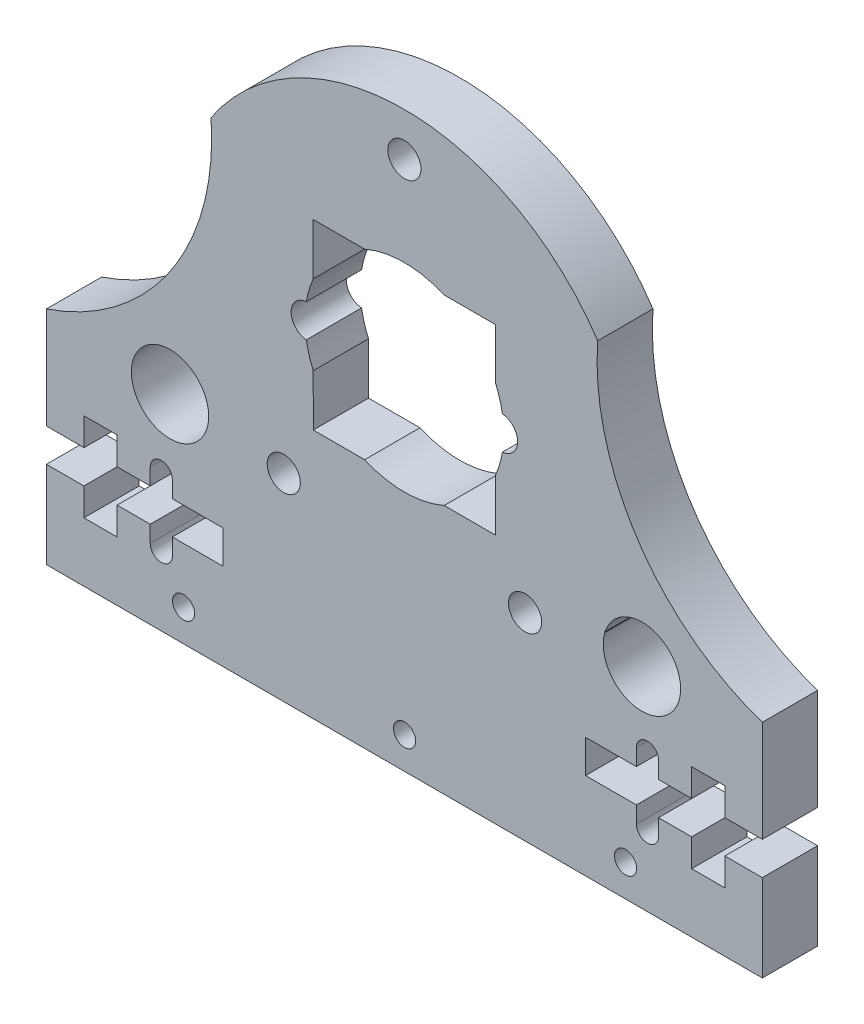
SolidWorks part; units mm, degrees
ref_plane "Front Plane" through (0, 0, 0) normal (0, 0, 1) x (1, 0, 0)
ref_plane "Top Plane" through (0, 0, 0) normal (0, 1, 0) x (1, 0, 0)
ref_plane "Right Plane" through (0, 0, 0) normal (1, 0, 0) x (0, 0, -1)
sketch "Sketch1" plane through (0, 0, 0) normal (0, 0, 1) x (1, 0, 0)
  line L0 (7.049, 19.6325) -> (17.9731, -10.4272)
  line L1 (-10.7531, -20.4888) -> (10.9241, -20.4888)
  line L2 (-7.0493, 19.6315) -> (-17.9689, -10.4301)
  line L68 (-32.396, -10.8383) -> (-32.396, -30.8817)
  line L69 (-32.396, -10.8383) -> (32.396, -10.8383)
  line L70 (32.396, -10.8383) -> (32.396, -30.8817)
  line L71 (-32.396, -30.8817) -> (32.396, -30.8817)
  line L72 (-32.396, -10.8383) -> (32.396, -30.8817) construction
  line L73 (32.396, -10.8383) -> (-32.396, -30.8817) construction
  line L83 (8.2458, 8.2543) -> (3.5926, 8.2519)
  line L84 (-3.6012, 8.2481) -> (-8.2543, 8.2457)
  line L85 (-8.2543, 8.2457) -> (-8.2519, 3.5926)
  line L86 (-8.2481, -3.6012) -> (-8.2457, -8.2543)
  line L87 (-8.2457, -8.2543) -> (-3.5926, -8.2519)
  line L88 (3.6012, -8.2481) -> (8.2543, -8.2457)
  line L89 (8.2543, -8.2457) -> (8.2519, -3.5217)
  line L90 (8.2481, 3.672) -> (8.2458, 8.2543)
  arc A0 (7.049, 19.6325) -> (-7.0493, 19.6315) centre (0, 17.0709) ccw
  arc A1 (10.9241, -20.4888) -> (17.9731, -10.4272) centre (10.9241, -12.9888) ccw
  arc A2 (-17.9689, -10.4301) -> (-10.7531, -20.4888) centre (-10.9196, -12.9907) ccw
  circle A3 centre (0, 17.0709) radius 1.5
  circle A4 centre (10.9241, -12.9888) radius 1.5
  circle A5 centre (-10.9196, -12.9907) radius 1.5
  arc A6 (-28.1118, -10.8383) -> (-16.6025, -6.6683) centre (-21.209, -11.9221) cw
  arc A7 (16.6787, -6.8654) -> (28.4035, -10.8383) centre (21.5008, -11.9221) cw
  circle A8 centre (0, 0.0709) radius 17 construction
  circle A78 centre (21.5008, -11.9221) radius 3.5
  circle A79 centre (-21.209, -11.9221) radius 3.5
  arc A94 (3.5926, 8.2519) -> (-3.6012, 8.2481) centre (0, 0) ccw
  arc A95 (-8.2519, 3.5926) -> (-8.8758, 1.4902) centre (0, 0) ccw
  arc A96 (-8.8758, 1.4902) -> (-8.8742, -1.4994) centre (-8.75, -0.0045) ccw
  arc A97 (-8.8742, -1.4994) -> (-8.2481, -3.6012) centre (0, 0) ccw
  arc A98 (-3.5926, -8.2519) -> (3.6012, -8.2481) centre (0, 0) ccw
  arc A99 (8.2519, -3.5217) -> (8.8758, -1.4193) centre (0, 0.0709) ccw
  arc A100 (8.8758, -1.4193) -> (8.8742, 1.5702) centre (8.75, 0.0754) ccw
  arc A101 (8.8742, 1.5702) -> (8.2481, 3.672) centre (0, 0.0709) ccw
  point P18 (0, -20.86)
  dimension "D1" = 15
  dimension "D2" = 7
  dimension "D3" = 34
extrude "Boss-Extrude1" add sketch "Sketch1" along normal blind 5 contours A79 L69 A78 L0 A0 L2 A101 A100 A99 L89 L88 A98 L87 L86 A97 A96 A95 L85 L84 A94 L83 L90 A3 | A79 A2 L1 A1 A78 L69 A5 A4 | A79 L69 L68 L71 L70 A78 A1 L1 A2 | A79 L2 A6 L69 | A78 L69 A7 L0 region at (11.3885, 6.2108, 0) region at (22.5052, -7.7427, 0) region at (-0.0256, -23.2651, 0) region at (-22.3529, -7.7149, 0) region at (0.0494, -15.5713, 0)
sketch "Sketch2" plane through (0, 0, 5) normal (0, 0, 1) x (1, 0, 0)
  line L0 (26.0003, -21.5138) -> (24.396, -21.5138) construction
  line L1 (26.0003, -17.5138) -> (29.0003, -17.5138)
  line L2 (26.0003, -25.5138) -> (26.0003, -17.5138)
  line L3 (29.0003, -17.5138) -> (29.0003, -25.5138)
  line L4 (29.0003, -25.5138) -> (26.0003, -25.5138)
  line L5 (32.396, -23.0138) -> (16.396, -23.0138)
  line L6 (32.396, -23.0138) -> (32.396, -20.0138)
  line L7 (32.396, -20.0138) -> (16.396, -20.0138)
  line L8 (16.396, -23.0138) -> (16.396, -20.0138)
  line L9 (32.396, -23.0138) -> (16.396, -20.0138) construction
  line L10 (32.396, -20.0138) -> (16.396, -23.0138) construction
  line L11 (22.0003, -18.5138) -> (22.0003, -24.5138) construction
  line L12 (23.0003, -18.5138) -> (23.0003, -24.5138)
  line L13 (21.0003, -18.5138) -> (21.0003, -24.5138)
  line L14 (32.396, -10.8383) -> (32.396, -30.8817) construction
  arc A0 (23.0003, -18.5138) -> (21.0003, -18.5138) centre (22.0003, -18.5138) ccw
  arc A1 (21.0003, -24.5138) -> (23.0003, -24.5138) centre (22.0003, -24.5138) ccw
  point P4 (24.396, -21.5138)
  point P17 (22.0003, -21.5138)
  dimension "D1" = 3
  dimension "D2" = 16
  dimension "D3" = 2
  dimension "D4" = 8
  dimension "D5" = 3
  dimension "D6" = 8
extrude "Cut-Extrude3" cut sketch "Sketch2" against normal blind 10 contours L2 L1 L3 L4 | L5 L8 L7 L6 | A1 L12 A0 L13
mirror "Mirror1" about plane through (0, 0, 0) normal (1, 0, 0) of "Cut-Extrude3"
sketch "Sketch3" plane through (0, 0, 5) normal (0, 0, 1) x (1, 0, 0)
  line L0 (-7.0493, 19.6315) -> (-16.6025, -6.6683) construction
  line L1 (7.049, 19.6325) -> (16.6787, -6.8654) construction
  arc A0 (-9.7788, 12.1172) -> (9.7807, 12.1157) centre (0, 0) cw
  circle A1 centre (0, 17.0709) radius 1.5 construction
extrude "Cut-Extrude4" [suppressed] cut sketch "Sketch3" against normal through all and the other way through all
sketch "Sketch4" plane through (0, 0, 5) normal (0, 0, 1) x (1, 0, 0)
  line L0 (-32.396, -10.8383) -> (-17.4976, 11.6118)
  line L1 (32.396, -10.8383) -> (17.4976, 11.6118)
  line L4 (-32.396, -10.8383) -> (-32.396, -30.8817)
  line L5 (-32.396, -30.8817) -> (32.396, -30.8817)
  line L6 (32.396, -10.8383) -> (32.396, -30.8817)
  line L40 (-28.1118, -10.8383) -> (-32.396, -10.8383)
  line L41 (-7.0493, 19.6315) -> (-16.6025, -6.6683)
  line L42 (-28.1118, -10.8383) -> (-32.396, -10.8383)
  line L43 (-7.0493, 19.6315) -> (-16.6025, -6.6683)
  line L46 (-7.0493, 19.6315) -> (-6.984, 19.8046)
  line L47 (7.049, 19.6325) -> (6.984, 19.8046)
  line L48 (28.4035, -10.8383) -> (32.396, -10.8383)
  line L49 (7.049, 19.6325) -> (16.6787, -6.8654)
  line L50 (28.4035, -10.8383) -> (32.396, -10.8383)
  line L51 (7.049, 19.6325) -> (16.6787, -6.8654)
  arc A0 (17.4976, 11.6118) -> (-17.4976, 11.6118) centre (0, 0) ccw
  arc A18 (-16.6025, -6.6683) -> (-28.1118, -10.8383) centre (-21.209, -11.9221) ccw
  arc A19 (-16.6025, -6.6683) -> (-28.1118, -10.8383) centre (-21.209, -11.9221) ccw
  arc A21 (7.049, 19.6325) -> (-7.0493, 19.6315) centre (0, 17.0709) ccw construction
  arc A22 (28.4035, -10.8383) -> (16.6787, -6.8654) centre (21.5008, -11.9221) ccw
  arc A23 (28.4035, -10.8383) -> (16.6787, -6.8654) centre (21.5008, -11.9221) ccw
  dimension "D1" = 42
  dimension "D2" = 0
  dimension "D3" = 0
extrude "Cut-Extrude5" cut sketch "Sketch4" against normal blind 10 flip side to cut contours L4 L5 L6 L1 A0 L0 region at (0.0169, -11.9101, 5)
extrude "Boss-Extrude2" add sketch "Sketch4<5>" against normal blind 5 contours A19 L43 L46 A0 L0 L42 | A23 L50 L1 A0 L47 L51 region at (-18.1813, 3.5961, 5) region at (18.12, 3.66, 5)
sketch "Sketch4<5>" plane through (0, 0, 5) normal (0, 0, 1) x (1, 0, 0) same geometry as "Sketch4"
sketch "Sketch5" plane through (0, 0, 5) normal (0, 0, 1) x (1, 0, 0)
  circle A0 centre (0.0146, -28) radius 1
  circle A1 centre (0.0146, -28) radius 1 construction
  circle A2 centre (20.0146, -27.9896) radius 1
  circle A3 centre (-19.9854, -28.0104) radius 1
  circle A4 centre (-19.9854, -28.0104) radius 1 construction
  circle A5 centre (20.0146, -27.9896) radius 1 construction
  dimension "D1" = 2
extrude "Cut-Extrude6" cut sketch "Sketch5" against normal blind 5
sketch "Sketch6" plane through (0, 0, 5) normal (0, 0, 1) x (1, 0, 0)
  line L0 (32.396, -10.8383) -> (17.4976, 11.6118) construction
  arc A0 (-32.396, -10.8383) -> (-17.4976, 11.6118) centre (-39.4388, 10.0039) ccw
  arc A1 (32.396, -10.8383) -> (17.4976, 11.6118) centre (39.4388, 10.0039) cw
  arc A4 (17.4976, 11.6118) -> (-17.4976, 11.6118) centre (0, 0) ccw construction
  arc A5 (-17.4976, 11.6118) -> (-32.396, -10.8383) centre (-17.2079, -4.7489) ccw
  arc A6 (17.4976, 11.6118) -> (32.396, -10.8383) centre (17.2493, -4.7215) cw
  dimension "D1" = 22
extrude "Cut-Extrude7" cut sketch "Sketch6" against normal through all
